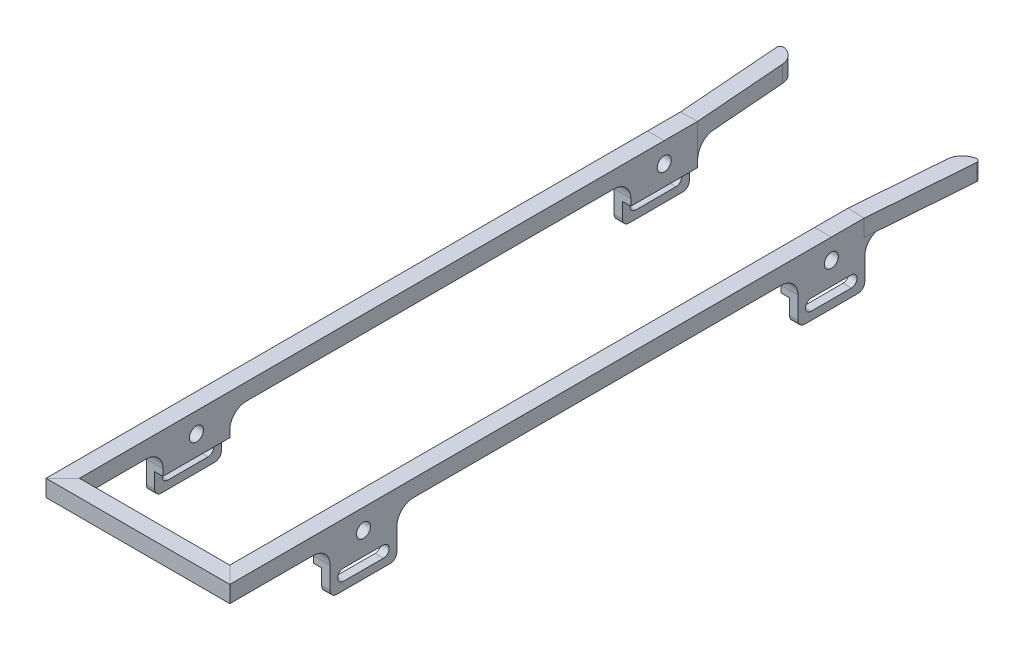
SolidWorks part; units mm, degrees
ref_plane "Front Plane" through (0, 0, 0) normal (0, 0, 1) x (1, 0, 0)
ref_plane "Top Plane" through (0, 0, 0) normal (0, 1, 0) x (1, 0, 0)
ref_plane "Right Plane" through (0, 0, 0) normal (1, 0, 0) x (0, 0, -1)
sketch "rail_path" plane through (0, 0, 0) normal (0, 1, 0) x (1, 0, 0)
  line L0 (28.575, 111.125) -> (28.575, 123.825)
  line L1 (-28.575, -111.125) -> (28.575, -111.125)
  line L2 (-28.575, -111.125) -> (-28.575, 111.125)
  line L3 (-28.575, 111.125) -> (28.575, 111.125) construction
  line L4 (28.575, -111.125) -> (28.575, 111.125)
  line L5 (-28.575, -111.125) -> (28.575, 111.125) construction
  line L6 (-28.575, 111.125) -> (28.575, -111.125) construction
  line L7 (-28.575, 111.125) -> (-28.575, 123.825)
  line L8 (28.575, 123.825) -> (31.75, 165.1)
  line L9 (-28.575, 123.825) -> (-31.75, 165.1)
  point P0 (0, 0)
  point P6 (0, 0)
  dimension "D1" = 222.25
  dimension "D2" = 57.15
  dimension "D3" = 12.7
  dimension "D4" = 12.7
  dimension "D5" = 41.275
  dimension "D6" = 3.175
  dimension "D7" = 3.175
sketch "rail_profile" plane through (0, 0, 0) normal (0, 0, 1) x (1, 0, 0)
  line L0 (-28.575, 0) -> (28.575, 0) construction
  line L1 (28.575, 0) -> (34.925, 0)
  line L2 (28.575, 0) -> (28.575, 6.35)
  line L3 (28.575, 6.35) -> (34.925, 6.35)
  line L4 (34.925, 0) -> (34.925, 6.35)
  line L5 (-28.575, 0) -> (28.575, 0) construction
  dimension "D1" = 6.35
  dimension "D2" = 6.35
sweep "Sweep1" add profiles "rail_profile" path "rail_path"
sketch "clip_profile" plane through (0, 0, 0) normal (0, 0, 1) x (1, 0, 0)
  line L4 (28.575, 0) -> (-28.575, 0)
  line L12 (-28.575, 6.35) -> (28.575, 6.35)
  line L34 (34.925, -17.272) -> (31.75, -17.272)
  line L38 (28.575, -8.89) -> (31.75, -8.89)
  line L39 (31.75, -17.272) -> (31.75, -8.89)
  line L47 (31.75, 6.35) -> (38.0813, 6.35)
  line L48 (34.925, -17.272) -> (34.925, -8.89)
  line L49 (38.0813, 6.35) -> (38.0813, 0)
  line L50 (28.575, -8.89) -> (34.925, -8.89)
  line L51 (28.575, -8.89) -> (28.575, 0)
  line L52 (28.575, 0) -> (34.925, 0)
  line L53 (34.925, -8.89) -> (34.925, 0)
  line L54 (31.75, 6.35) -> (38.0813, 6.35)
  line L55 (38.0813, 6.35) -> (38.0813, 0)
  line L56 (38.0813, 0) -> (31.75, 0)
  line L57 (31.75, 0) -> (28.575, 0)
  line L58 (38.0813, 0) -> (31.75, 0)
  line L59 (-28.575, 0) -> (-31.75, 0)
  line L60 (-31.75, 0) -> (-38.0813, 0)
  line L61 (-38.0813, 0) -> (-38.0813, 6.35)
  line L62 (-38.0813, 6.35) -> (-31.75, 6.35)
  line L63 (-31.75, 6.35) -> (-28.575, 6.35)
  line L64 (31.75, 0) -> (28.575, 0)
  line L65 (28.575, 6.35) -> (31.75, 6.35)
  line L66 (-28.575, 0) -> (-31.75, 0)
  line L67 (-31.75, 0) -> (-38.0813, 0)
  line L68 (-38.0813, 0) -> (-38.0813, 6.35)
  line L69 (-38.0813, 6.35) -> (-31.75, 6.35)
  line L70 (-31.75, 6.35) -> (-28.575, 6.35)
  line L71 (28.575, 6.35) -> (31.75, 6.35)
  dimension "D1" = 8.89
  dimension "D2" = 3.175
  dimension "D4" = 8.382
ref_plane "BackClipPlane" through (0, 0, 66.675) normal (0, 0, -1) x (-1, 0, 0)
ref_plane "FrontClipPlane" through (0, 0, -111.125) normal (0, 0, -1) x (-1, 0, 0)
sketch "BackClipProfile" plane through (0, 0, 66.675) normal (0, 0, -1) x (-1, 0, 0)
  line L24 (-34.925, -8.89) -> (-34.925, 0) construction
  line L25 (-34.925, -17.272) -> (-34.925, -8.89) construction
  line L26 (-34.925, -17.272) -> (-31.75, -17.272) construction
  line L27 (-31.75, -17.272) -> (-31.75, -8.89) construction
  line L28 (-28.575, -8.89) -> (-31.75, -8.89) construction
  line L29 (-28.575, -8.89) -> (-28.575, 0) construction
  line L30 (-34.925, -8.89) -> (-34.925, 0)
  line L31 (-34.925, -17.272) -> (-34.925, -8.89)
  line L32 (-34.925, -17.272) -> (-31.75, -17.272)
  line L33 (-31.75, -17.272) -> (-31.75, -8.89)
  line L34 (-28.575, -8.89) -> (-31.75, -8.89)
  line L35 (-28.575, -8.89) -> (-28.575, 0)
  line L36 (-28.575, 0) -> (-34.925, 0)
sketch "FrontClipProfile" plane through (0, 0, -111.125) normal (0, 0, -1) x (-1, 0, 0)
  line L24 (-31.75, -17.272) -> (-31.75, -8.89) construction
  line L25 (-34.925, -17.272) -> (-31.75, -17.272) construction
  line L26 (-34.925, -17.272) -> (-34.925, -8.89) construction
  line L27 (-34.925, -8.89) -> (-34.925, 0) construction
  line L28 (-28.575, -8.89) -> (-31.75, -8.89) construction
  line L29 (-28.575, -8.89) -> (-28.575, 0) construction
  line L30 (-31.75, -17.272) -> (-31.75, -8.89)
  line L31 (-34.925, -17.272) -> (-31.75, -17.272)
  line L32 (-34.925, -17.272) -> (-34.925, -8.89)
  line L33 (-34.925, -8.89) -> (-34.925, 0)
  line L34 (-28.575, -8.89) -> (-31.75, -8.89)
  line L35 (-28.575, -8.89) -> (-28.575, 0)
  line L36 (-28.575, 0) -> (-34.925, 0)
extrude "BackClip" add sketch "BackClipProfile" along normal mid plane 25.4
mirror "BackClipMirror" about plane through (0, 0, 0) normal (1, 0, 0) of "BackClip"
extrude "FrontClip" add sketch "FrontClipProfile" along normal mid plane 25.4
mirror "FrontClipMirror" about plane through (0, 0, 0) normal (1, 0, 0) of "FrontClip"
sketch "Sketch8" plane through (28.575, 0, 0) normal (-1, 0, 0) x (0, 0, 1)
  line L0 (53.975, -8.89) -> (79.375, 6.35) construction
  line L1 (111.125, 6.35) -> (-111.125, 6.35) construction
  line L9 (111.125, 6.35) -> (-111.125, 6.35) construction
  line L17 (111.125, 6.35) -> (-111.125, 6.35) construction
  circle A2 centre (66.675, -1.27) radius 2.667
  point P4 (0, 0)
  dimension "D2" = 5.334
extrude "Cut-Extrude1" cut sketch "Sketch8" against normal through all both and the other way through all
ref_plane "Plane1" through (0, 0, -22.225) normal (0, 0, -1) x (-1, 0, 0)
sketch "Sketch10" plane through (31.75, 0, 0) normal (-1, 0, 0) x (0, 0, 1)
  line L0 (59.055, -12.065) -> (74.295, -12.065) construction
  line L1 (59.055, -9.906) -> (74.295, -9.906)
  line L2 (59.055, -14.224) -> (74.295, -14.224)
  line L3 (53.975, -8.89) -> (79.375, -8.89) construction
  line L4 (66.675, 3.4925) -> (66.675, -3.4925) construction
  arc A0 (59.055, -9.906) -> (59.055, -14.224) centre (59.055, -12.065) ccw
  arc A1 (74.295, -14.224) -> (74.295, -9.906) centre (74.295, -12.065) ccw
  point P2 (66.675, -12.065)
  point P9 (0, 0)
  point P12 (0, 0)
  point P15 (0, 0)
  point P16 (0, 0)
  dimension "D2" = 2.159
  dimension "D1" = 3.175
  dimension "D3" = 15.24
fillet "Fillet1" radius 2.54 8 edges at (-33.3375, -17.272, -123.825) (-33.3375, -17.272, -98.425) (-33.3375, -17.272, 53.975) (-33.3375, -17.272, 79.375) (33.3375, -17.272, 53.975) (33.3375, -17.272, 79.375) (33.3375, -17.272, -98.425) (33.3375, -17.272, -123.825)
mirror "Mirror2" about plane through (0, 0, -22.225) normal (0, 0, -1) of "Cut-Extrude1"
extrude "Cut-Extrude3" cut sketch "Sketch10" against normal through all both and the other way through all
mirror "Mirror3" about plane through (0, 0, -22.225) normal (0, 0, -1) of "Cut-Extrude3"
fillet "Fillet3" radius 6.35 2 edges at (31.75, 3.175, -165.1) (-31.75, 3.175, -165.1)
fillet "Fillet5" radius 1.27 2 edges at (38.0813, 3.175, -164.613) (-38.0813, 3.175, -164.613)
fillet "Fillet10" radius 6.35 8 edges at (-31.75, 0, 53.975) (-31.75, 0, 79.375) (31.75, 0, 79.375) (31.75, 0, 53.975) (31.75, 0, -98.425) (-31.75, 0, -98.425) (31.75, 0, -123.825) (-31.75, 0, -123.825)
equation "\"rail_horizontal_clearance\"= 0.25 / 2"
